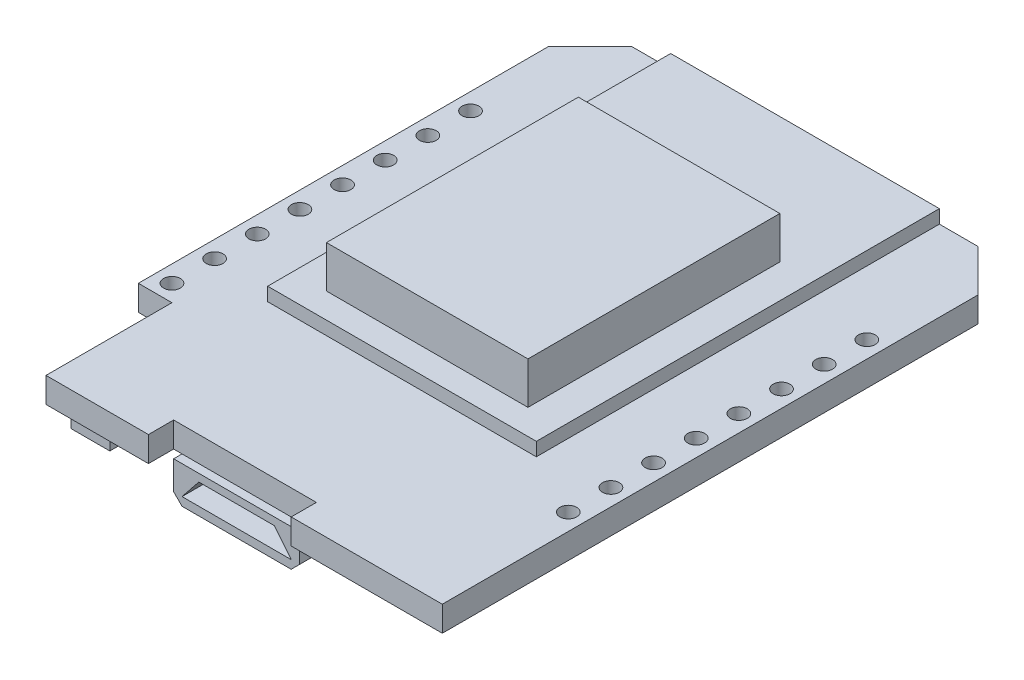
SolidWorks part; units mm, degrees
note: The reader was unsure of these and kept them because the rebuilt part matched: shared geometry of "Sketch5<4>", "Sketch5<5>", "Sketch5<6>".
other "PCB"
other "USB Micro"
ref_plane "Front Plane" through (0, 0, 0) normal (0, 0, 1) x (1, 0, 0)
ref_plane "Top Plane" through (0, 0, 0) normal (0, 1, 0) x (1, 0, 0)
ref_plane "Right Plane" through (0, 0, 0) normal (1, 0, 0) x (0, 0, -1)
sketch "Sketch1" plane through (0, 0, 0) normal (0, 1, 0) x (1, 0, 0)
  line L0 (0, 0) -> (0, 31.9)
  line L1 (0, 31.9) -> (-2.5, 34.4)
  line L2 (-2.5, 34.4) -> (-23.1, 34.4)
  line L3 (-23.1, 34.4) -> (-25.6, 31.9)
  line L4 (-25.6, 31.9) -> (-25.6, 7.5)
  line L5 (-25.6, 7.5) -> (-23.6, 7.5)
  line L6 (-23.6, 7.5) -> (-23.6, 0)
  line L7 (0, 0) -> (-9, 0)
  line L8 (-9, 0) -> (-9, 1.5)
  line L9 (-9, 1.5) -> (-17.5, 1.5)
  line L10 (-17.5, 1.5) -> (-17.5, 0)
  line L11 (-17.5, 0) -> (-23.6, 0)
  line L12 (-1, -1.7092) -> (-1, 37.7939) construction
  line L13 (-24.6, 37.7939) -> (-24.6, -1.7092) construction
  line L14 (-28.0763, 8.5) -> (2.6406, 8.5) construction
  circle A0 centre (-24.6, 8.5) radius 0.5
  circle A1 centre (-1, 8.5) radius 0.5
  circle A2 centre (-24.6, 11.04) radius 0.5
  circle A3 centre (-1, 11.04) radius 0.5
  circle A4 centre (-24.6, 13.58) radius 0.5
  circle A5 centre (-1, 13.58) radius 0.5
  circle A6 centre (-24.6, 16.12) radius 0.5
  circle A7 centre (-1, 16.12) radius 0.5
  circle A8 centre (-24.6, 18.66) radius 0.5
  circle A9 centre (-1, 18.66) radius 0.5
  circle A10 centre (-24.6, 21.2) radius 0.5
  circle A11 centre (-1, 21.2) radius 0.5
  circle A12 centre (-24.6, 23.74) radius 0.5
  circle A13 centre (-1, 23.74) radius 0.5
  circle A14 centre (-24.6, 26.28) radius 0.5
  circle A15 centre (-1, 26.28) radius 0.5
  dimension "D13" = 1
  dimension "D1" = 25.6
  dimension "D2" = 34.4
  dimension "D3" = 2.5
  dimension "D4" = 2.5
  dimension "D5" = 7.5
  dimension "D6" = 2
  dimension "D7" = 8.5
  dimension "D8" = 1.5
  dimension "D9" = 9
  dimension "D10" = 1
  dimension "D11" = 1
  dimension "D12" = 8.5
  dimension "D14" = 8
extrude "PCB" add sketch "Sketch1" along normal blind 1.5
sketch "Sketch2" plane through (0, 1.5, 0) normal (0, 1, 0) x (1, 0, 0)
  line L0 (-2.5, 34.4) -> (-23.1, 34.4) construction
  line L1 (-20.8, 34.4) -> (-4.8, 34.4)
  line L2 (-20.8, 34.4) -> (-20.8, 10.4)
  line L3 (-20.8, 10.4) -> (-4.8, 10.4)
  line L4 (-4.8, 34.4) -> (-4.8, 10.4)
  point P6 (-12.8, 34.4)
  point P7 (-12.8, 34.4)
  point P8 (-12.8, 34.4)
  point P9 (-12.8, 34.4)
  point P10 (-12.8, 34.4)
  point P11 (-12.8, 34.4)
  point P12 (-4.8, 31.3326)
  dimension "D1" = 24
  dimension "D2" = 16
extrude "ESP8266 PCB" add sketch "Sketch2" along normal blind 0.8 separate body
sketch "Sketch3" plane through (0, 2.3, 0) normal (0, 1, 0) x (1, 0, 0)
  line L0 (-4.8, 34.4) -> (-20.8, 34.4) construction
  line L1 (-18.8, 11.9) -> (-6.8, 11.9)
  line L2 (-18.8, 11.9) -> (-18.8, 26.9)
  line L3 (-18.8, 26.9) -> (-6.8, 26.9)
  line L4 (-6.8, 11.9) -> (-6.8, 26.9)
  point P4 (-12.8, 34.4)
  point P5 (-12.8, 26.9)
  dimension "D1" = 12
  dimension "D2" = 15
  dimension "D3" = 7.5
extrude "ESP8266 Rf Shield" add sketch "Sketch3" along normal blind 2.5 separate body
sketch "Sketch5" plane through (0, 0, 0) normal (0, -1, 0) x (1, 0, 0)
  line L0 (-23.6, -7.5) -> (-23.6, 0) construction
  line L1 (-23.6, -1.5) -> (-21.3, -1.5)
  line L2 (-23.6, -1.5) -> (-23.6, -6)
  line L3 (-23.6, -6) -> (-21.3, -6)
  line L4 (-21.3, -1.5) -> (-21.3, -6)
  line L5 (-3.9144, -3.7056) -> (-2.4144, -3.7056)
  line L6 (-17, -1) -> (-9.5, -1)
  line L7 (-17, -1) -> (-17, -6.6)
  line L8 (-17, -6.6) -> (-9.5, -6.6)
  line L9 (-9.5, -1) -> (-9.5, -6.6)
  line L10 (-3.9144, -3.7056) -> (-3.9144, -2.7056)
  line L11 (-18.7643, -9.825) -> (-8.6486, -9.825)
  line L12 (-18.7643, -9.825) -> (-18.7643, -14.4)
  line L13 (-18.7643, -14.4) -> (-8.6486, -14.4)
  line L14 (-8.6486, -9.825) -> (-8.6486, -14.4)
  line L15 (-2.5, -34.4) -> (-23.1, -34.4) construction
  line L16 (-20.1, -28.4) -> (-18.6, -28.4)
  line L17 (-20.1, -28.4) -> (-20.1, -27.4)
  line L18 (-20.1, -27.4) -> (-18.6, -27.4)
  line L19 (-3.9144, -2.7056) -> (-2.4144, -2.7056)
  line L20 (-2.4144, -3.7056) -> (-2.4144, -2.7056)
  line L21 (-6.0768, -10.9216) -> (-6.0768, -9.4216)
  line L22 (-6.0768, -10.9216) -> (-7.0768, -10.9216)
  line L23 (-7.0768, -10.9216) -> (-7.0768, -9.4216)
  line L24 (-6.0768, -9.4216) -> (-7.0768, -9.4216)
  line L25 (-4.477, -10.9216) -> (-4.477, -9.4216)
  line L26 (-4.477, -10.9216) -> (-5.477, -10.9216)
  line L27 (-5.477, -10.9216) -> (-5.477, -9.4216)
  line L28 (-4.477, -9.4216) -> (-5.477, -9.4216)
  line L29 (-7.3592, -3.3369) -> (-7.3592, -1.8369)
  line L30 (-7.3592, -3.3369) -> (-8.3592, -3.3369)
  line L31 (-17.5, -1.5) -> (-9, -1.5) construction
  line L32 (-18.6, -28.4) -> (-18.6, -27.4)
  line L33 (-25.6, -31.9) -> (-25.6, -7.5) construction
  line L34 (-13.6, -28.4) -> (-12.1, -28.4)
  line L35 (-13.6, -28.4) -> (-13.6, -27.4)
  line L36 (-13.6, -27.4) -> (-12.1, -27.4)
  line L37 (-12.1, -28.4) -> (-12.1, -27.4)
  line L38 (-7.1, -28.4) -> (-5.6, -28.4)
  line L39 (-7.1, -28.4) -> (-7.1, -27.4)
  line L40 (-7.1, -27.4) -> (-5.6, -27.4)
  line L41 (-5.6, -28.4) -> (-5.6, -27.4)
  line L42 (-13.6, -26.4) -> (-12.1, -26.4) [skipped]
  line L43 (-13.6, -26.4) -> (-13.6, -25.4) [skipped]
  line L44 (-13.6, -25.4) -> (-12.1, -25.4) [skipped]
  line L45 (-12.1, -26.4) -> (-12.1, -25.4) [skipped]
  line L46 (-7.1, -26.4) -> (-5.6, -26.4)
  line L47 (-7.1, -26.4) -> (-7.1, -25.4)
  line L48 (-7.1, -25.4) -> (-5.6, -25.4)
  line L49 (-5.6, -26.4) -> (-5.6, -25.4)
  line L50 (-13.6, -24.4) -> (-12.1, -24.4)
  line L51 (-13.6, -24.4) -> (-13.6, -23.4)
  line L52 (-13.6, -23.4) -> (-12.1, -23.4)
  line L53 (-12.1, -24.4) -> (-12.1, -23.4)
  line L54 (-7.1, -24.4) -> (-5.6, -24.4) [skipped]
  line L55 (-7.1, -24.4) -> (-7.1, -23.4) [skipped]
  line L56 (-7.1, -23.4) -> (-5.6, -23.4) [skipped]
  line L57 (-5.6, -24.4) -> (-5.6, -23.4) [skipped]
  line L58 (-13.6, -22.4) -> (-12.1, -22.4)
  line L59 (-13.6, -22.4) -> (-13.6, -21.4)
  line L60 (-13.6, -21.4) -> (-12.1, -21.4)
  line L61 (-12.1, -22.4) -> (-12.1, -21.4)
  line L62 (-7.1, -22.4) -> (-5.6, -22.4) [skipped]
  line L63 (-7.1, -22.4) -> (-7.1, -21.4) [skipped]
  line L64 (-7.1, -21.4) -> (-5.6, -21.4) [skipped]
  line L65 (-5.6, -22.4) -> (-5.6, -21.4) [skipped]
  line L66 (-13.6, -20.4) -> (-12.1, -20.4) [skipped]
  line L67 (-13.6, -20.4) -> (-13.6, -19.4) [skipped]
  line L68 (-13.6, -19.4) -> (-12.1, -19.4) [skipped]
  line L69 (-12.1, -20.4) -> (-12.1, -19.4) [skipped]
  line L70 (-7.1, -20.4) -> (-5.6, -20.4)
  line L71 (-7.1, -20.4) -> (-7.1, -19.4)
  line L72 (-7.1, -19.4) -> (-5.6, -19.4)
  line L73 (-5.6, -20.4) -> (-5.6, -19.4)
  line L74 (-13.6, -18.4) -> (-12.1, -18.4)
  line L75 (-13.6, -18.4) -> (-13.6, -17.4)
  line L76 (-13.6, -17.4) -> (-12.1, -17.4)
  line L77 (-12.1, -18.4) -> (-12.1, -17.4)
  line L78 (-7.1, -18.4) -> (-5.6, -18.4)
  line L79 (-7.1, -18.4) -> (-7.1, -17.4)
  line L80 (-7.1, -17.4) -> (-5.6, -17.4)
  line L81 (-5.6, -18.4) -> (-5.6, -17.4)
  line L82 (-13.6, -16.4) -> (-12.1, -16.4) [skipped]
  line L83 (-13.6, -16.4) -> (-13.6, -15.4) [skipped]
  line L84 (-13.6, -15.4) -> (-12.1, -15.4) [skipped]
  line L85 (-12.1, -16.4) -> (-12.1, -15.4) [skipped]
  line L86 (-7.1, -16.4) -> (-5.6, -16.4)
  line L87 (-7.1, -16.4) -> (-7.1, -15.4)
  line L88 (-7.1, -15.4) -> (-5.6, -15.4)
  line L89 (-5.6, -16.4) -> (-5.6, -15.4)
  line L90 (-13.6, -14.4) -> (-12.1, -14.4) [skipped]
  line L91 (-13.6, -14.4) -> (-13.6, -13.4) [skipped]
  line L92 (-13.6, -13.4) -> (-12.1, -13.4) [skipped]
  line L93 (-12.1, -14.4) -> (-12.1, -13.4) [skipped]
  line L94 (-7.1, -14.4) -> (-5.6, -14.4)
  line L95 (-7.1, -14.4) -> (-7.1, -13.4)
  line L96 (-7.1, -13.4) -> (-5.6, -13.4)
  line L97 (-5.6, -14.4) -> (-5.6, -13.4)
  line L98 (-20.1, -26.4) -> (-18.6, -26.4)
  line L99 (-20.1, -26.4) -> (-20.1, -25.4)
  line L100 (-20.1, -25.4) -> (-18.6, -25.4)
  line L101 (-18.6, -26.4) -> (-18.6, -25.4)
  line L102 (-20.1, -24.4) -> (-18.6, -24.4)
  line L103 (-20.1, -24.4) -> (-20.1, -23.4)
  line L104 (-20.1, -23.4) -> (-18.6, -23.4)
  line L105 (-18.6, -24.4) -> (-18.6, -23.4)
  line L106 (-20.1, -22.4) -> (-18.6, -22.4)
  line L107 (-20.1, -22.4) -> (-20.1, -21.4)
  line L108 (-20.1, -21.4) -> (-18.6, -21.4)
  line L109 (-18.6, -22.4) -> (-18.6, -21.4)
  line L110 (-20.1, -20.4) -> (-18.6, -20.4)
  line L111 (-20.1, -20.4) -> (-20.1, -19.4)
  line L112 (-20.1, -19.4) -> (-18.6, -19.4)
  line L113 (-18.6, -20.4) -> (-18.6, -19.4)
  line L114 (-20.1, -18.4) -> (-18.6, -18.4)
  line L115 (-20.1, -18.4) -> (-20.1, -17.4)
  line L116 (-20.1, -17.4) -> (-18.6, -17.4)
  line L117 (-18.6, -18.4) -> (-18.6, -17.4)
  line L118 (-20.1, -16.4) -> (-18.6, -16.4)
  line L119 (-20.1, -16.4) -> (-20.1, -15.4)
  line L120 (-20.1, -15.4) -> (-18.6, -15.4)
  line L121 (-18.6, -16.4) -> (-18.6, -15.4)
  line L122 (-20.1, -14.4) -> (-18.6, -14.4) [skipped]
  line L123 (-20.1, -14.4) -> (-20.1, -13.4) [skipped]
  line L124 (-20.1, -13.4) -> (-18.6, -13.4) [skipped]
  line L125 (-18.6, -14.4) -> (-18.6, -13.4) [skipped]
  line L126 (-23.6, 0) -> (-17.5, 0) construction
  line L127 (-8.3592, -3.3369) -> (-8.3592, -1.8369)
  line L128 (-7.3592, -1.8369) -> (-8.3592, -1.8369)
  line L129 (-5.4144, -1.8369) -> (-3.9144, -1.8369)
  line L130 (-5.4144, -1.8369) -> (-5.4144, -0.8369)
  line L131 (-5.4144, -0.8369) -> (-3.9144, -0.8369)
  line L132 (-3.9144, -1.8369) -> (-3.9144, -0.8369)
  line L133 (-7.2524, -7.3947) -> (-7.2524, -5.8947)
  line L134 (-7.2524, -7.3947) -> (-8.2524, -7.3947)
  line L135 (-8.2524, -7.3947) -> (-8.2524, -5.8947)
  line L136 (-7.2524, -5.8947) -> (-8.2524, -5.8947)
  line L137 (-4.3695, -7.2325) -> (-2.8695, -7.2325)
  line L138 (-4.3695, -7.2325) -> (-4.3695, -6.2325)
  line L139 (-4.3695, -6.2325) -> (-2.8695, -6.2325)
  line L140 (-2.8695, -7.2325) -> (-2.8695, -6.2325)
  line L141 (-18.357, -8.0394) -> (-18.357, -5.3089)
  line L142 (-18.357, -8.0394) -> (-19.357, -8.0394)
  line L143 (-19.357, -8.0394) -> (-19.357, -5.3089)
  line L144 (-18.357, -5.3089) -> (-19.357, -5.3089)
  line L145 (-9, 0) -> (0, 0) construction
  line L146 (-20.1, -28.4) -> (-13.6, -28.4) construction
  line L147 (-20.1, -28.4) -> (-20.1, -26.4) construction
  point P38 (-13.25, -1.5)
  point P131 (-13.25, -1)
  point P132 (-13.25, -1.5)
  dimension "D1" = 1.5
  dimension "D2" = 1
  dimension "D3" = 6
  dimension "D4" = 5.5
  dimension "D6" = 2.3
  dimension "D7" = 4.5
  dimension "D8" = 1.5
  dimension "D9" = 8
  dimension "D10" = 7.5
  dimension "D11" = 5.6
  dimension "D12" = 90
  dimension "D13" = 6.5
  dimension "D14" = 2
  dimension "D5" = 3
extrude "Boss-Extrude4" add sketch "Sketch5" along normal blind 2.2 separate body contours L7 L8 L9 L6
chamfer "Chamfer1" distance 0.5 angle 45 2 edges at (-9.5, -2.2, -3.8) (-17, -2.2, -3.8)
sketch "Sketch12" plane through (0, 0, -1) normal (0, 0, 1) x (1, 0, 0)
  line L0 (-15.5, -0.45) -> (-11, -0.45)
  line L1 (-11, -0.45) -> (-10, -1.7)
  line L2 (-10, -1.7) -> (-16.5, -1.7)
  line L3 (-16.5, -1.7) -> (-15.5, -0.45)
  line L4 (-17, 0) -> (-9.5, 0) construction
  line L5 (-16.5, -2.2) -> (-10, -2.2) construction
  line L6 (-9.5, -1.7) -> (-9.5, 0) construction
  point P2 (-13.25, -0.45)
  point P5 (-13.25, 0)
  point P6 (-13.25, -1.7)
  point P9 (-13.25, -2.2)
  dimension "D1" = 0.5
  dimension "D2" = 1.5
  dimension "D3" = 0.5
  dimension "D4" = 1.75
extrude "Cut-Extrude1" cut sketch "Sketch12" against normal blind 4 from surface at 0 starting at face at (-13.25, -1.3, -1)
extrude "Button Body" add sketch "Sketch5<4>" along normal blind 2 from surface at 0 separate body starting at face at (-24.6, 0, -25.78)
sketch "Sketch5<4>" plane through (0, 0, 0) normal (0, -1, 0) x (1, 0, 0) same geometry as "Sketch5"
sketch "Sketch11" plane through (-23.6, 0, 0) normal (-1, 0, 0) x (0, 0, 1)
  line L0 (-6, -2) -> (-1.5, 0) construction
  line L1 (-6, 0) -> (-1.5, -2) construction
  line L2 (-7.5, 0) -> (0, 0) construction
  line L3 (-4.75, -1.4475) -> (-2.75, -1.4475)
  line L4 (-4.75, -1.4475) -> (-4.75, -0.5525)
  line L5 (-4.75, -0.5525) -> (-2.75, -0.5525)
  line L6 (-2.75, -1.4475) -> (-2.75, -0.5525)
  line L7 (-4.75, -1.4475) -> (-2.75, -0.5525) construction
  line L8 (-4.75, -0.5525) -> (-2.75, -1.4475) construction
  line L9 (-6, 0) -> (-1.5, 0) construction
  point P8 (-3.75, -1)
  point P9 (-3.75, -1)
  dimension "D1" = 2
  dimension "D2" = 0.5525
  dimension "D3" = 1.25
  dimension "D4" = 1
  dimension "D5" = 2
extrude "Button Actuator" add sketch "Sketch11" along normal blind 1 separate body
extrude "Components1" add sketch "Sketch5<5>" along normal blind 1 from surface at 0 separate body contours L5 L20 L19 L10 | L14 L11 L12 L13 | L34 L37 L36 L35 | L74 L77 L76 L75 | L29 L128 L127 L30 starting at face at (-24.6, 0, -25.78)
sketch "Sketch5<5>" plane through (0, 0, 0) normal (0, -1, 0) x (1, 0, 0) same geometry as "Sketch5"
extrude "Components 2" add sketch "Sketch5<6>" along normal blind 0.5 from surface at 0 separate body contours L118 L121 L120 L119 | L114 L117 L116 L115 | L110 L113 L112 L111 | L106 L109 L108 L107 | L102 L105 L104 L103 | L98 L101 L100 L99 | L16 L32 L18 L17 | L50 L53 L52 L51 | L58 L61 L60 L59 | L141 L144 L143 L142 | L129 L132 L131 L130 | L133 L136 L135 L134 | L137 L140 L139 L138 | L25 L28 L27 L26 | L21 L24 L23 L22 | L94 L97 L96 L95 | L86 L89 L88 L87 | L78 L81 L80 L79 | L70 L73 L72 L71 | L46 L49 L48 L47 | L38 L41 L40 L39 starting at face at (-24.6, 0, -25.78)
sketch "Sketch5<6>" plane through (0, 0, 0) normal (0, -1, 0) x (1, 0, 0) same geometry as "Sketch5"
sketch "Sketch13" plane through (0, 0, 0) normal (0, -1, 0) x (-1, 0, 0)
  line L0 (12.8, 38.7908) -> (12.8, -3.1035) construction
  line L1 (2.5, 34.4) -> (23.1, 34.4) construction
  point P3 (12.8, 34.4)
